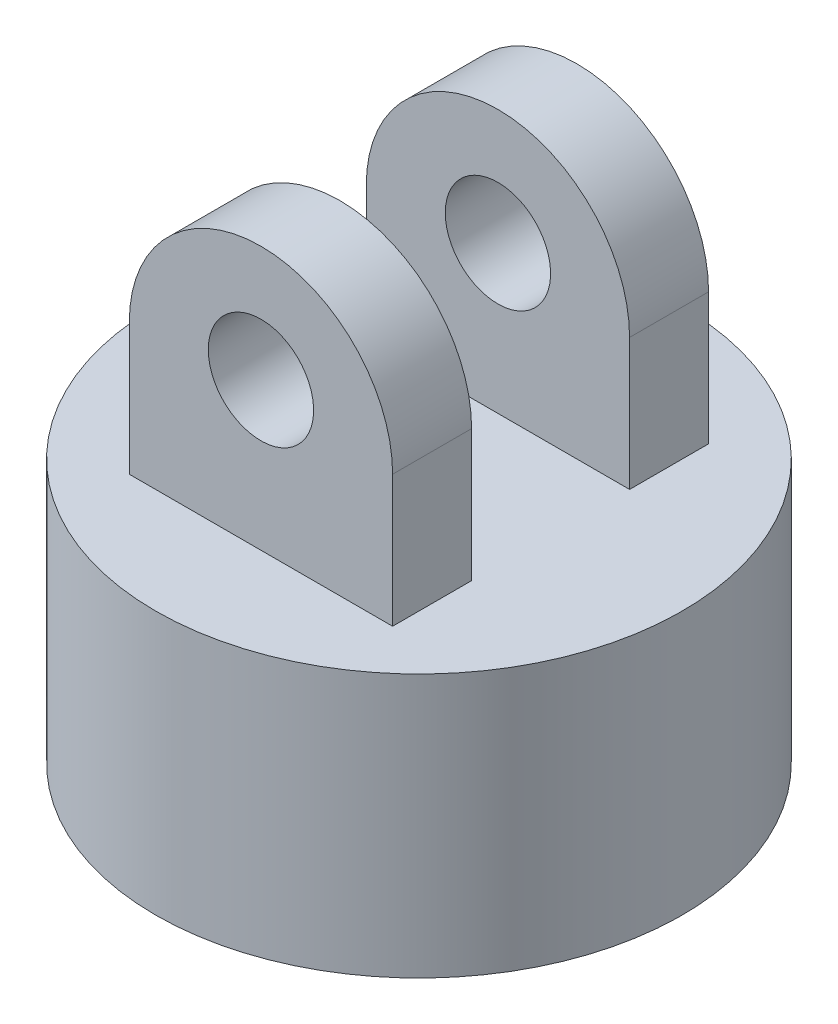
SolidWorks part; units mm, degrees
ref_plane "Alzado" through (0, 0, 0) normal (0, 0, 1) x (1, 0, 0)
ref_plane "Planta" through (0, 0, 0) normal (0, 1, 0) x (1, 0, 0)
ref_plane "Vista lateral" through (0, 0, 0) normal (1, 0, 0) x (0, 0, -1)
sketch "Croquis1" plane through (0, 0, 0) normal (0, 1, 0) x (1, 0, 0)
  circle A0 centre (0, 0) radius 50
  dimension "D1" = 100
extrude "Saliente-Extruir1" add sketch "Croquis1" along normal blind 50
sketch "Croquis2" plane through (0, 50, 0) normal (0, 1, 0) x (1, 0, 0)
  line L0 (-50, 0) -> (50, 0) construction
  line L1 (0, 50) -> (0, -50) construction
  line L2 (-25, 30) -> (25, 30)
  line L3 (25, 30) -> (25, 15)
  line L4 (25, 15) -> (-25, 15)
  line L5 (-25, 15) -> (-25, 30)
  line L6 (-25, -15) -> (-25, -30)
  line L7 (-25, -30) -> (25, -30)
  line L8 (25, -30) -> (25, -15)
  line L9 (25, -15) -> (-25, -15)
  circle A0 centre (0, 0) radius 50 construction
  point P13 (25, 22.5)
  dimension "D1" = 30
  dimension "D2" = 15
  dimension "D3" = 50
  dimension "D4" = 50
  dimension "D5" = 25
  dimension "D6" = 60
  dimension "D7" = 15
extrude "Saliente-Extruir2" add sketch "Croquis2" along normal blind 50
sketch "Croquis4" plane through (0, 0, -30) normal (0, 0, -1) x (-1, 0, 0)
  line L0 (25, 100) -> (25, 50) construction
  line L1 (-25, 100) -> (25, 100) construction
  circle A0 centre (0, 78) radius 10
  dimension "D1" = 20
  dimension "D2" = 25
  dimension "D3" = 22
extrude "Cortar-Extruir1" cut sketch "Croquis4" against normal blind 60
fillet "Redondeo1" 2 edges at (25, 100, -22.5) (-25, 100, -22.5) type full round first side face at (25, 75, -22.5) second side face at (-25, 75, -22.5) middle face at (0, 100, -22.5)
fillet "Redondeo2" 2 edges at (25, 100, 22.5) (-25, 100, 22.5) type full round first side face at (25, 75, 22.5) second side face at (-25, 75, 22.5) middle face at (0, 100, 22.5)
